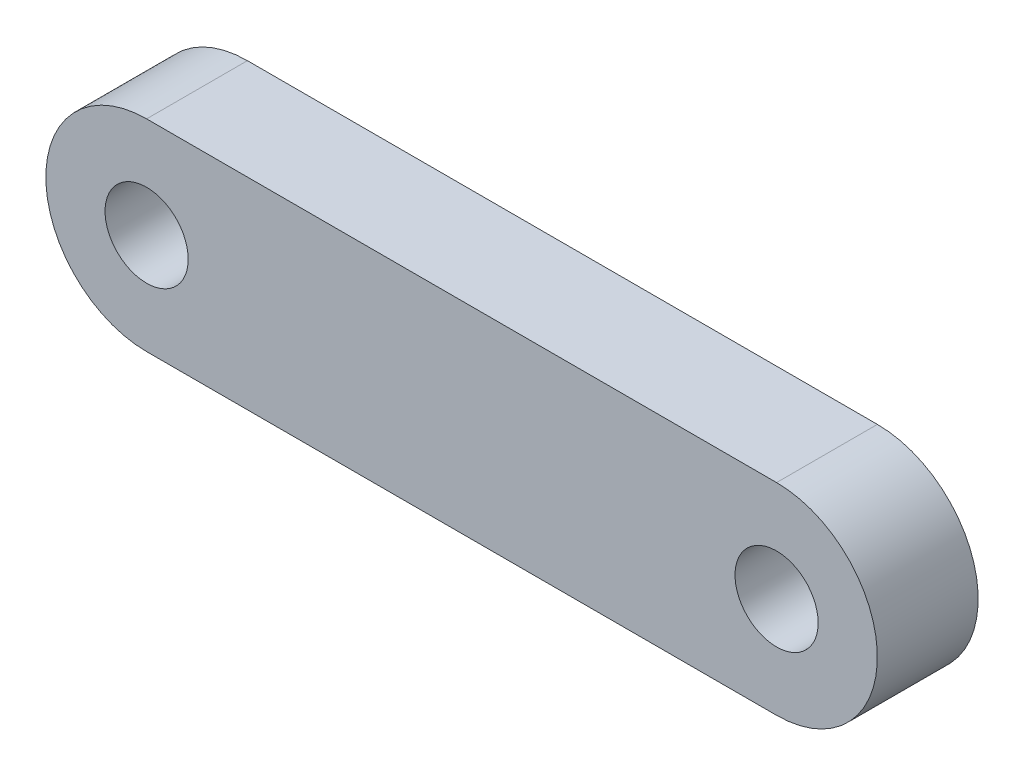
SolidWorks part; units mm, degrees
ref_plane "Front Plane" through (0, 0, 0) normal (0, 0, 1) x (1, 0, 0)
ref_plane "Top Plane" through (0, 0, 0) normal (0, 1, 0) x (1, 0, 0)
ref_plane "Right Plane" through (0, 0, 0) normal (1, 0, 0) x (0, 0, -1)
sketch "Sketch1" plane through (0, 0, 0) normal (0, 0, 1) x (1, 0, 0)
  line L0 (-25, 4) -> (0, 4)
  line L1 (-25, -4) -> (0, -4)
  arc A0 (0, -4) -> (0, 4) centre (0, 0) ccw
  circle A1 centre (0, 0) radius 1.65
  circle A2 centre (-25, 0) radius 1.65
  arc A3 (-25, 4) -> (-25, -4) centre (-25, 0) ccw
  dimension "D1" = 8
  dimension "D2" = 3.3
  dimension "D3" = 25
extrude "Boss-Extrude1" add sketch "Sketch1" along normal blind 4
